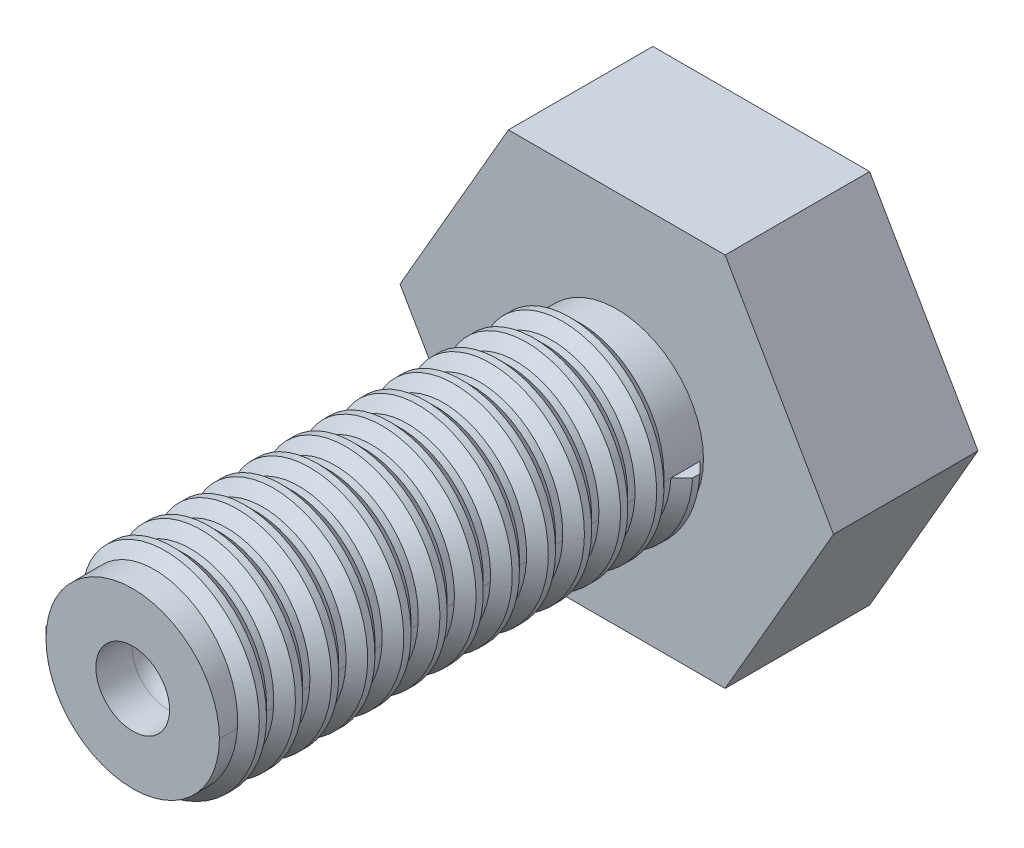
SolidWorks part; units mm, degrees
ref_plane "前视基准面" through (0, 0, 0) normal (0, 0, 1) x (1, 0, 0)
ref_plane "上视基准面" through (0, 0, 0) normal (0, 1, 0) x (1, 0, 0)
ref_plane "右视基准面" through (0, 0, 0) normal (1, 0, 0) x (0, 0, -1)
other "Configuration Table"
sketch "草图1" plane through (0, 0, 0) normal (0, 0, 1) x (1, 0, 0)
  line L13 (15, 0) -> (7.5, 12.9904)
  line L14 (7.5, 12.9904) -> (-7.5, 12.9904)
  line L15 (-7.5, 12.9904) -> (-15, 0)
  line L16 (-15, 0) -> (-7.5, -12.9904)
  line L17 (-7.5, -12.9904) -> (7.5, -12.9904)
  line L18 (7.5, -12.9904) -> (15, 0)
  circle A0 centre (0, 0) radius 15 construction
  dimension "D1" = 30
extrude "凸台-拉伸1" add sketch "草图1" along normal blind 10
sketch "草图2" plane through (0, 0, 10) normal (0, 0, 1) x (1, 0, 0)
  circle A0 centre (0, 0) radius 6
  dimension "D1" = 12
extrude "凸台-拉伸2" add sketch "草图2" along normal blind 33.5
ref_plane "基准面1" through (0, 0, 11.25) normal (0, 0, 1) x (1, 0, 0)
sketch "草图3" plane through (0, 0, 11.25) normal (0, 0, 1) x (1, 0, 0)
  circle A0 centre (0, 0) radius 6 construction
  circle A1 centre (0, 0) radius 6
curve "螺旋线/涡状线1" pitch 2.5 height 31.25 radius 6 left hand yes centre (0, 0, 11.25) axis (0, 0, 1) start towards (1, 0, 0)
sketch "草图4" plane through (0, 0, 0) normal (0, 1, 0) x (1, 0, 0)
  line L0 (6, -10.25) -> (6, -12.25)
  line L1 (6, -12.25) -> (6.75, -11.5)
  line L2 (6.75, -11.5) -> (6.75, -11)
  line L3 (6.75, -11) -> (6, -10.25)
  point P6 (6, -11.25)
  dimension "D1" = 0.75
  dimension "D2" = 2
  dimension "D3" = 45
  dimension "D4" = 45
sweep "扫描1" add profiles "草图4" path "螺旋线/涡状线1"
sketch "草图10" plane through (0, 0, 43.5) normal (0, 0, 1) x (1, 0, 0)
  circle A0 centre (0, 0) radius 2.55
  dimension "D1" = 5.1
extrude "切除-拉伸1" cut sketch "草图10" against normal blind 2.5
sketch "草图11" plane through (0, 0, 41) normal (0, 0, 1) x (1, 0, 0)
  line L0 (0, 2.55) -> (0, -2.55)
  arc A3 (0, -2.55) -> (0, 2.55) centre (0, 0) ccw
  dimension "D1" = 5.1
revolve "切除-旋转1" cut sketch "草图11" angle 360 about L0
